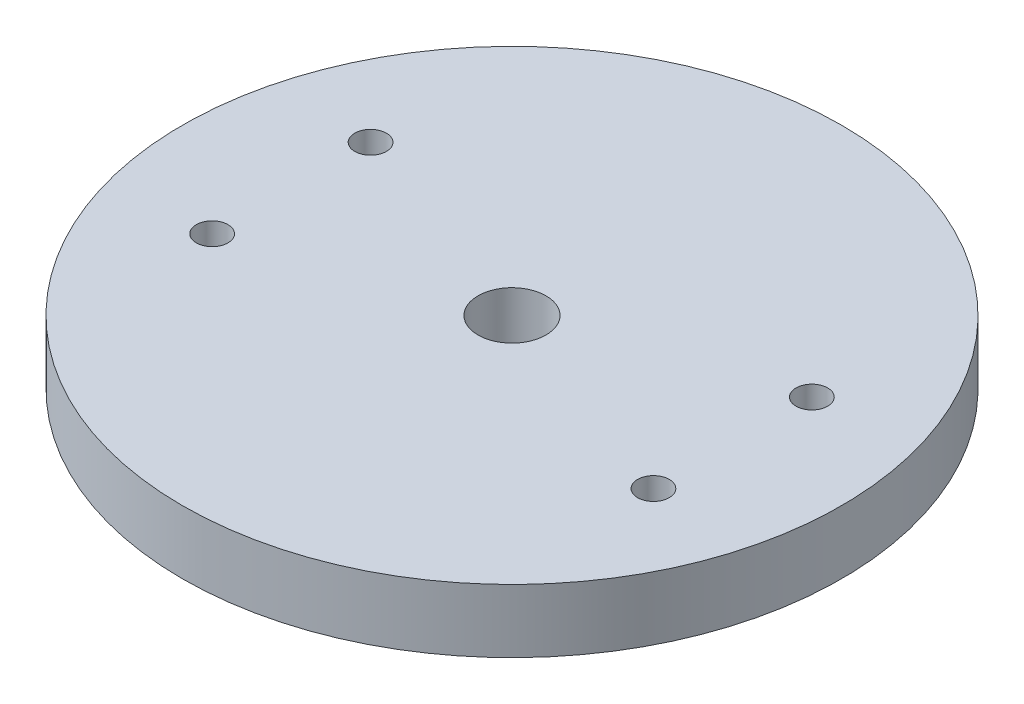
SolidWorks part; units mm, degrees
ref_plane "Front Plane" through (0, 0, 0) normal (0, 0, 1) x (1, 0, 0)
ref_plane "Top Plane" through (0, 0, 0) normal (0, 1, 0) x (1, 0, 0)
ref_plane "Right Plane" through (0, 0, 0) normal (1, 0, 0) x (0, 0, -1)
sketch "Sketch1" plane through (0, 0, 0) normal (0, 1, 0) x (1, 0, 0)
  circle A0 centre (0, 0) radius 66.04
  dimension "D1" = 132.08
extrude "Boss-Extrude1" add sketch "Sketch1" along normal blind 12.7
sketch "Sketch3" plane through (0, 12.7, 0) normal (0, 1, 0) x (1, 0, 0)
  circle A0 centre (0, 0) radius 63.5
  dimension "D1" = 127
sketch "Sketch2" plane through (0, 12.7, 0) normal (0, 1, 0) x (1, 0, 0)
  line L0 (-72.7941, 0) -> (72.3878, 0) construction
  line L1 (0, 70.7385) -> (0, -72.4581) construction
  circle A0 centre (-44.2148, 15.875) radius 3.175
  circle A1 centre (-44.2148, -15.875) radius 3.175
  circle A2 centre (44.2148, -15.875) radius 3.175
  circle A3 centre (44.2148, 15.875) radius 3.175
  dimension "D1" = 6.35
  dimension "D2" = 15.875
extrude "Cut-Extrude1" cut sketch "Sketch2" against normal through all and the other way through all
sketch "Sketch4" plane through (0, 0, 0) normal (0, -1, 0) x (1, 0, 0)
  circle A0 centre (0, 0) radius 6.8107
extrude "Cut-Extrude2" cut sketch "Sketch4" against normal through all
